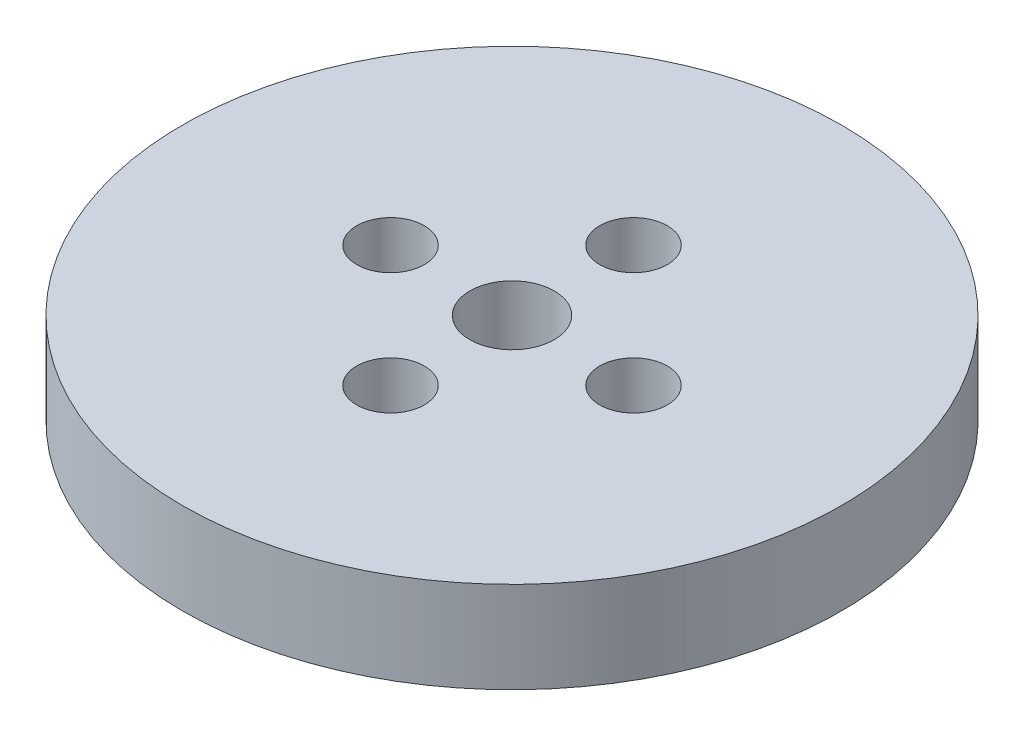
SolidWorks part; units mm, degrees
ref_plane "Front Plane" through (0, 0, 0) normal (0, 0, 1) x (1, 0, 0)
ref_plane "Top Plane" through (0, 0, 0) normal (0, 1, 0) x (1, 0, 0)
ref_plane "Right Plane" through (0, 0, 0) normal (1, 0, 0) x (0, 0, -1)
sketch "Sketch1" plane through (0, 0, 0) normal (0, 1, 0) x (1, 0, 0)
  circle A0 centre (0, 0) radius 97.5
  dimension "FLANGE_OD" = 195
extrude "Boss-Extrude1" add sketch "Sketch1" along normal blind 27
sketch "Sketch2" plane through (0, 0, 0) normal (0, 1, 0) x (1, 0, 0)
  circle A0 centre (0, 0) radius 12.5
  dimension "BORE_D" = 25
extrude "Cut-Extrude1" cut sketch "Sketch2" along normal through all
sketch "Sketch3" plane through (0, 27, 0) normal (0, 1, 0) x (1, 0, 0)
  circle A0 centre (0, 0) radius 35.9447 construction
  circle A1 centre (-35.9447, 0) radius 10
  dimension "BOLT_D" = 20
  dimension "BOLT_PCD" = 71.8894
extrude "Cut-Extrude2" cut sketch "Sketch3" against normal blind 18.781
pattern_circular "CirPattern1" count 4 over 360 about axis through (0, 0, 0) along (0, 1, 0) of "Cut-Extrude2"
